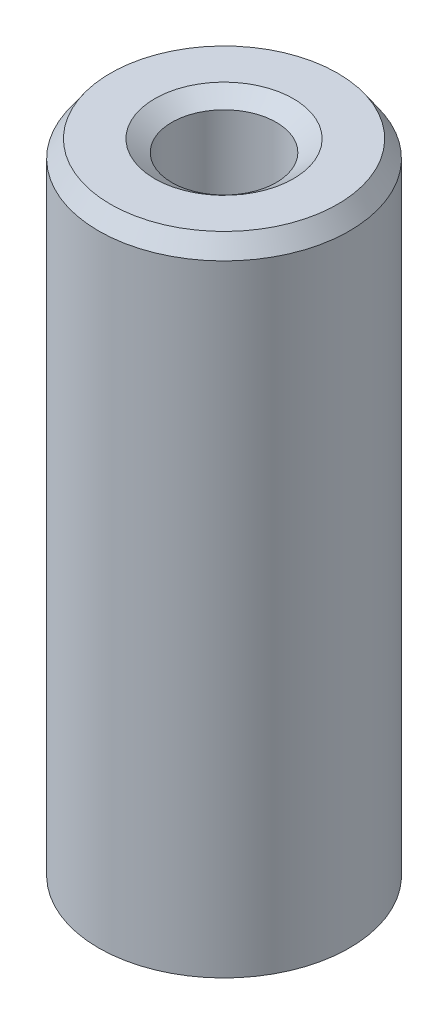
SolidWorks part; units mm, degrees
ref_plane "Front Plane" through (0, 0, 0) normal (0, 0, 1) x (1, 0, 0)
ref_plane "Top Plane" through (0, 0, 0) normal (0, 1, 0) x (1, 0, 0)
ref_plane "Right Plane" through (0, 0, 0) normal (1, 0, 0) x (0, 0, -1)
sketch "Sketch1" plane through (0, 0, 0) normal (0, 1, 0) x (1, 0, 0)
  circle A0 centre (0, 0) radius 7.5
  dimension "SLEEVE_OD" = 15
extrude "Boss-Extrude1" add sketch "Sketch1" along normal blind 38.8572
sketch "Sketch2" plane through (0, 0, 0) normal (0, 1, 0) x (1, 0, 0)
  circle A0 centre (0, 0) radius 3.1218
  dimension "BORE_D" = 6.2436
extrude "Cut-Extrude1" cut sketch "Sketch2" along normal through all
chamfer "Chamfer1" distance 1.0256 angle 34.68 4 edges at (0, 38.8572, 3.1218) (0, 0, 3.1218) (0, 0, 7.5) (0, 38.8572, 7.5) first distance on face at (0, 38.8572, 3.1218) first distance on face at (0, 0, 3.1218) first distance on face at (0, 38.8572, 7.5)
